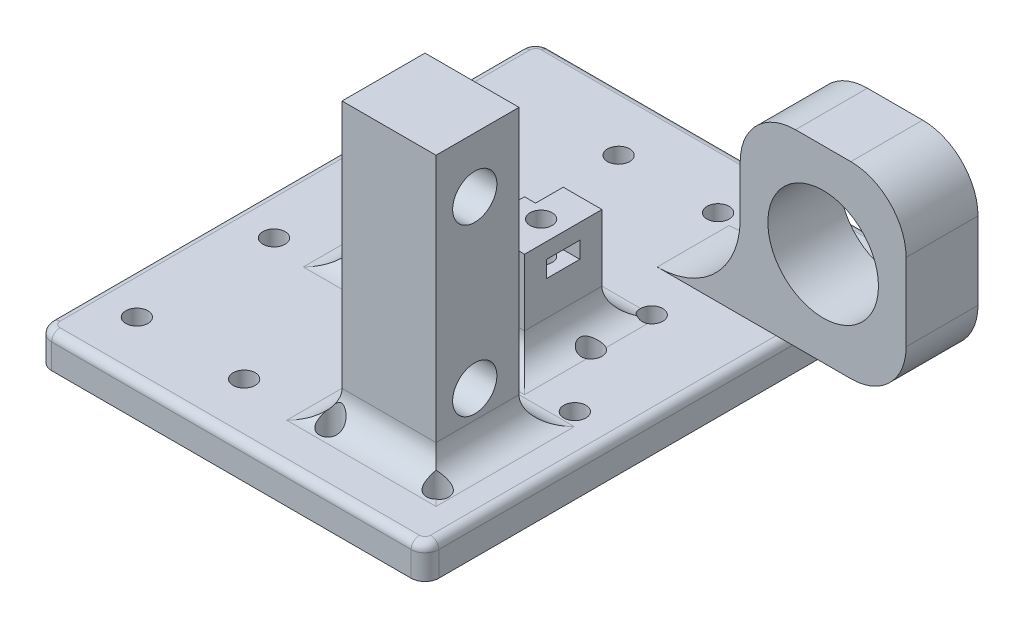
SolidWorks part; units mm, degrees
ref_plane "Front Plane" through (0, 0, 0) normal (0, 0, 1) x (1, 0, 0)
ref_plane "Top Plane" through (0, 0, 0) normal (0, 1, 0) x (1, 0, 0)
ref_plane "Right Plane" through (0, 0, 0) normal (1, 0, 0) x (0, 0, -1)
sketch "Sketch1" plane through (0, 0, 0) normal (0, 1, 0) x (1, 0, 0)
  line L0 (-8.0156, -1.4008) -> (61.9844, -1.4008)
  line L1 (-8.0156, 43.5992) -> (61.9844, 43.5992)
  line L2 (-8.0156, 43.5992) -> (-8.0156, -46.4008)
  line L3 (-8.0156, -46.4008) -> (61.9844, -46.4008)
  line L4 (61.9844, 43.5992) -> (61.9844, -46.4008)
  line L5 (26.9844, 43.5992) -> (26.9844, -46.4008)
  line L6 (9.4844, -1.4008) -> (9.4844, -46.4008)
  line L7 (-8.0156, -23.9008) -> (61.9844, -23.9008)
  circle A0 centre (17.9844, 32.5992) radius 3
  circle A1 centre (17.9844, 32.5992) radius 2
  circle A2 centre (18.095, 8.5992) radius 3
  circle A3 centre (18.095, 8.5992) radius 2
  circle A4 centre (35.8739, 8.5992) radius 2
  circle A5 centre (35.8739, 8.5992) radius 3
  circle A6 centre (35.9844, 32.5992) radius 2
  circle A7 centre (35.9844, 32.5992) radius 3
  circle A8 centre (19.1844, -11.5008) radius 2
  circle A9 centre (19.1844, -11.5008) radius 3
  circle A10 centre (-0.2156, -11.5008) radius 3
  circle A11 centre (-0.2156, -11.5008) radius 2
  circle A12 centre (-0.2156, -36.3008) radius 2
  circle A13 centre (19.1844, -36.3008) radius 3
  circle A14 centre (19.1844, -36.3008) radius 2
  circle A15 centre (-0.2156, -36.3008) radius 3
  circle A16 centre (54.1844, -36.3008) radius 2
  circle A17 centre (54.1844, -36.3008) radius 3
  circle A18 centre (34.7844, -36.3008) radius 2
  circle A19 centre (34.7844, -36.3008) radius 3
  circle A20 centre (34.7844, -11.5008) radius 3
  circle A21 centre (34.7844, -11.5008) radius 2
  circle A22 centre (54.1844, -11.5008) radius 2
  circle A23 centre (54.1844, -11.5008) radius 3
  dimension "D3" = 9
  dimension "D1" = 90
  dimension "D2" = 70
  dimension "D4" = 11
  dimension "D5" = 24
  dimension "D6" = 10.1
  dimension "D7" = 7.8
  dimension "D8" = 17.5
  dimension "D9" = 22.5
extrude "Boss-Extrude1" add sketch "Sketch1" along normal blind 6 contours L5 L1 L2 L0 A2 A0 | L1 L5 L0 L4 A5 A7 | A7 A6 | A0 A1 | A2 A3 | A5 A4 | L7 L6 L3 L5 A13 | L6 L7 L5 L0 A9 | L2 L7 L6 L0 A10 | L5 L7 L4 L0 A20 A23 | L7 L5 L3 L4 A17 A19 | L7 L2 L3 L6 A15 | A10 A11 | A9 A8 | A20 A21 | A23 A22 | A17 A16 | A13 A14 | A15 A12 | A19 | A18 region at (9.1658, 0, -21.1178) region at (0.7344, 0, 1.6858) region at (18.2344, 0, 1.6858) region at (0.7344, 0, 24.1858) region at (44.803, 0, -21.1178) region at (44.4844, 0, 12.7397) region at (18.2344, 0, 24.1858) region at (44.4844, 0, 35.0618) region at (15.0693, 0, -32.5992) region at (15.1799, 0, -8.5992) region at (32.9587, 0, -8.5992) region at (33.0693, 0, -32.5992) region at (16.2693, 0, 11.5008) region at (-3.1307, 0, 11.5008) region at (16.2693, 0, 36.3008) region at (-3.1307, 0, 36.3008) region at (51.2693, 0, 36.3008) region at (31.8693, 0, 11.5008) region at (51.2693, 0, 11.5008)
sketch "Sketch3" plane through (0, 6, 0) normal (0, 1, 0) x (1, 0, 0)
  line L0 (26.9844, 43.5992) -> (26.9844, -46.4008)
  line L1 (11.9844, 5.5992) -> (41.9844, 5.5992)
  line L2 (11.9844, 5.5992) -> (11.9844, -8.4008)
  line L3 (11.9844, -8.4008) -> (41.9844, -8.4008)
  line L4 (41.9844, 5.5992) -> (41.9844, -8.4008)
  line L5 (-8.0156, 43.5992) -> (61.9844, 43.5992) construction
  line L6 (-8.0156, -46.4008) -> (61.9844, -46.4008) construction
  line L7 (-8.0156, -1.4008) -> (61.9844, -1.4008)
  line L8 (-8.0156, 43.5992) -> (-8.0156, -46.4008) construction
  line L9 (61.9844, 43.5992) -> (61.9844, -46.4008) construction
  dimension "D1" = 14
  dimension "D2" = 30
  dimension "D3" = 7
  dimension "D4" = 15
extrude "Boss-Extrude2" add sketch "Sketch3" along normal blind 17 contours L2 L7 L0 L1 | L0 L7 L4 L1 | L7 L0 L3 L4 | L7 L2 L3 L0 region at (34.4844, 6, -2.0992) region at (19.4844, 6, -2.0992) region at (34.4844, 6, 4.9008) region at (19.4844, 6, 4.9008)
fillet "Fillet1" radius 2.5 4 edges at (-8.0156, 3, -43.5992) (61.9844, 3, -43.5992) (61.9844, 3, 46.4008) (-8.0156, 3, 46.4008)
fillet "Fillet2" radius 1.5 8 edges at (26.9844, 6, -43.5992) (-7.2833, 6, 45.6685) (61.2522, 6, 45.6685) (26.9844, 6, 46.4008) (61.2522, 6, -42.867) (61.9844, 6, 1.4008) (-7.2833, 6, -42.867) (-8.0156, 6, 1.4008)
sketch "Sketch4" plane through (0, 23, 0) normal (0, 1, 0) x (1, 0, 0)
  line L0 (26.9844, 42.0992) -> (26.9844, -44.9008)
  line L1 (59.4844, 42.0992) -> (-5.5156, 42.0992) construction
  line L2 (-5.5156, -44.9008) -> (59.4844, -44.9008) construction
  line L3 (-6.5156, -1.4008) -> (60.4844, -1.4008)
  line L4 (-6.5156, 41.0992) -> (-6.5156, -43.9008) construction
  line L5 (60.4844, -43.9008) -> (60.4844, 41.0992) construction
  circle A0 centre (15.9844, -1.4008) radius 2
  circle A1 centre (37.9844, -1.4008) radius 2
  dimension "D1" = 11
extrude "Cut-Extrude1" cut sketch "Sketch4" against normal blind 22 contours L3 A0 | L3 A0 | A1 L3 | A1 L3 region at (15.9844, 23, 0.552) region at (37.9844, 23, 0.552) region at (37.9844, 23, 2.2496) region at (15.9844, 23, 2.2496)
sketch "Sketch5" plane through (0, 0, -5.5992) normal (0, 0, -1) x (-1, 0, 0)
  line L0 (-11.9844, 23) -> (-41.9844, 23) construction
  line L1 (-34.9844, 23) -> (-18.9844, 23)
  line L2 (-11.9844, 6) -> (-41.9844, 6) construction
  circle A0 centre (-26.9844, 23) radius 8
  circle A1 centre (-26.9844, 23) radius 6
extrude "Cut-Extrude2" cut sketch "Sketch5" against normal blind 22 contours A1
sketch "Sketch6" plane through (0, 0, -5.5992) normal (0, 0, -1) x (-1, 0, 0)
  line L0 (-18.9844, 23) -> (-34.9844, 23)
  circle A0 centre (-26.9844, 23) radius 8
  circle A1 centre (-26.9844, 23) radius 6
  circle A2 centre (-26.9844, 23) radius 6
  circle A3 centre (-26.9844, 23) radius 8
  arc M1 (-20.9844, 23) -> (-32.9844, 23) centre (-26.9844, 23) cw
  line M2 (-32.9844, 23) -> (-41.9844, 23)
  line M6 (-11.9844, 23) -> (-20.9844, 23)
  dimension "D1" = 12
  dimension "D2" = 16
extrude "Cut-Extrude4" cut sketch "Sketch6" against normal blind 5 contours A0 M2 M6 M1 region at (26.9844, 15.1789, -5.5992)
sketch "Sketch9" plane through (0, 0, 8.4008) normal (0, 0, 1) x (1, 0, 0)
  circle A0 centre (26.9844, 23) radius 6
  circle A1 centre (26.9844, 23) radius 8
extrude "Cut-Extrude5" cut sketch "Sketch9" against normal blind 5
fillet "Fillet3" radius 5 4 edges at (26.9844, 6, 8.4008) (11.9844, 6, 1.4008) (26.9844, 6, -5.5992) (41.9844, 6, 1.4008)
sketch "Sketch10" plane through (0, 6, 0) normal (0, 1, 0) x (1, 0, 0)
  line L0 (53.9844, 42.0992) -> (53.9844, -44.9008)
  line L1 (59.4844, 42.0992) -> (-5.5156, 42.0992) construction
  line L2 (-5.5156, -44.9008) -> (59.4844, -44.9008) construction
  line L3 (26.9844, 43.5992) -> (26.9844, -46.4008)
  line L4 (-5.5156, 43.5992) -> (59.4844, 43.5992) construction
  line L5 (59.4844, -46.4008) -> (-5.5156, -46.4008) construction
  line L6 (26.9844, -1.4008) -> (60.4844, -1.4008)
  line L7 (53.9844, 31.5992) -> (83.9844, 31.5992)
  line L8 (53.9844, 31.5992) -> (53.9844, 18.5992)
  line L9 (53.9844, 18.5992) -> (83.9844, 18.5992)
  line L10 (83.9844, 31.5992) -> (83.9844, 18.5992)
  line L11 (60.4844, -43.9008) -> (60.4844, 41.0992) construction
  dimension "D1" = 27
  dimension "D2" = 30
  dimension "D3" = 20
  dimension "D4" = 13
extrude "Boss-Extrude5" add sketch "Sketch10" along normal blind 34 contours L7 L10 L9 L8
sketch "Sketch13" plane through (0, 0, -18.5992) normal (0, 0, 1) x (1, 0, 0)
  line L0 (68.9844, 40) -> (68.9844, 6)
  line L1 (53.9844, 40) -> (83.9844, 40) construction
  line L2 (60.4844, 6) -> (83.9844, 6) construction
  line L3 (53.9844, 23) -> (83.9844, 23)
  line L4 (53.9844, 40) -> (53.9844, 6) construction
  line L5 (83.9844, 40) -> (83.9844, 6) construction
  circle A0 centre (68.9844, 23) radius 10
extrude "Cut-Extrude6" cut sketch "Sketch13" against normal blind 34 contours L0 A0 L3 | L3 A0 L0 | L0 A0 L3 | L3 A0 L0 region at (73.2286, 27.2441, -18.5992) region at (64.7403, 27.2441, -18.5992) region at (73.2286, 18.7559, -18.5992) region at (64.7403, 18.7559, -18.5992)
fillet "Fillet5" radius 10 3 edges at (83.9844, 6, -25.0992) (53.9844, 40, -25.0992) (83.9844, 40, -25.0992)
sketch "Sketch14" plane through (0, 6, 0) normal (0, 1, 0) x (1, 0, 0)
  line L0 (-5.5156, -44.9008) -> (59.4844, -44.9008) construction
  line L1 (51.4844, -33.9008) -> (34.4844, -33.9008)
  line L2 (51.4844, -33.9008) -> (51.4844, -18.9008)
  line L3 (51.4844, -18.9008) -> (34.4844, -18.9008)
  line L4 (34.4844, -33.9008) -> (34.4844, -18.9008)
  line L5 (60.4844, -43.9008) -> (60.4844, 18.5992) construction
  dimension "D1" = 15
  dimension "D2" = 11
  dimension "D3" = 17
  dimension "D4" = 9
extrude "Boss-Extrude6" add sketch "Sketch14" along normal blind 50
sketch "Sketch15" plane through (51.4844, 0, 0) normal (1, 0, 0) x (0, 0, -1)
  line L0 (-33.9008, 6) -> (-18.9008, 6) construction
  line L1 (-33.9008, 56) -> (-33.9008, 6) construction
  circle A0 centre (-26.9008, 16) radius 4
  circle A1 centre (-26.9008, 46) radius 4
  dimension "D1" = 30
  dimension "D2" = 10
  dimension "D3" = 7
  dimension "D4" = 7
extrude "Cut-Extrude7" cut sketch "Sketch15" against normal blind 12
sketch "Sketch17" plane through (51.4844, 0, 0) normal (1, 0, 0) x (0, 0, -1)
  circle A0 centre (-26.9008, 46) radius 2.5
  circle A1 centre (-26.9008, 16) radius 2.5
extrude "Cut-Extrude8" cut sketch "Sketch17" against normal blind 30
fillet "Fillet9" radius 5 4 edges at (51.4844, 6, 26.4008) (42.9844, 6, 18.9008) (34.4844, 6, 26.4008) (42.9844, 6, 33.9008)
sketch "Sketch19" plane through (41.9844, 0, 0) normal (1, 0, 0) x (0, 0, -1)
  line L0 (5.5992, 23) -> (-8.4008, 23) construction
  line L1 (-4.4008, 20.2) -> (1.5992, 20.2)
  line L2 (-4.4008, 20.2) -> (-4.4008, 17.2)
  line L3 (-4.4008, 17.2) -> (1.5992, 17.2)
  line L4 (1.5992, 20.2) -> (1.5992, 17.2)
  line L5 (-8.4008, 23) -> (-8.4008, 11) construction
  point P6 (-8.4008, 17)
  dimension "D1" = 3
  dimension "D2" = 6
  dimension "D3" = 2.8
  dimension "D4" = 4
extrude "Cut-Extrude9" cut sketch "Sketch19" against normal blind 6.5
sketch "Sketch20" plane through (11.9844, 0, 0) normal (-1, 0, 0) x (0, 0, 1)
  line L0 (-5.5992, 23) -> (8.4008, 23) construction
  line L1 (-1.5992, 20.2) -> (4.4008, 20.2)
  line L2 (-1.5992, 20.2) -> (-1.5992, 17.2)
  line L3 (-1.5992, 17.2) -> (4.4008, 17.2)
  line L4 (4.4008, 20.2) -> (4.4008, 17.2)
  line L5 (8.4008, 23) -> (8.4008, 11) construction
  dimension "D1" = 6
  dimension "D2" = 3
  dimension "D3" = 2.8
  dimension "D4" = 4
extrude "Cut-Extrude10" cut sketch "Sketch20" against normal blind 6.5
fillet "Fillet10" radius 15 1 edges at (53.9844, 6, -25.0992)
sketch "Sketch22" plane through (0, 6, 0) normal (0, 1, 0) x (1, 0, 0)
  line L0 (-8.0156, -43.9008) -> (-8.0156, 41.0992) construction
  line L1 (-5.5156, 43.5992) -> (59.4844, 43.5992) construction
  circle A0 centre (7.9844, 10.5992) radius 2
  circle A1 centre (7.9844, 10.5992) radius 3
  circle A2 centre (45.9844, 10.5992) radius 3
  circle A3 centre (45.9844, 10.5992) radius 2
  circle A4 centre (45.9844, -0.4008) radius 3
  circle A5 centre (45.9844, -0.4008) radius 2
  circle A6 centre (7.9844, -0.4008) radius 2
  circle A7 centre (7.9844, -0.4008) radius 3
  dimension "D1" = 16
  dimension "D2" = 33
extrude "Cut-Extrude14" cut sketch "Sketch22" against normal through all both and the other way through all contours A6 | A0 | A3 | A5
